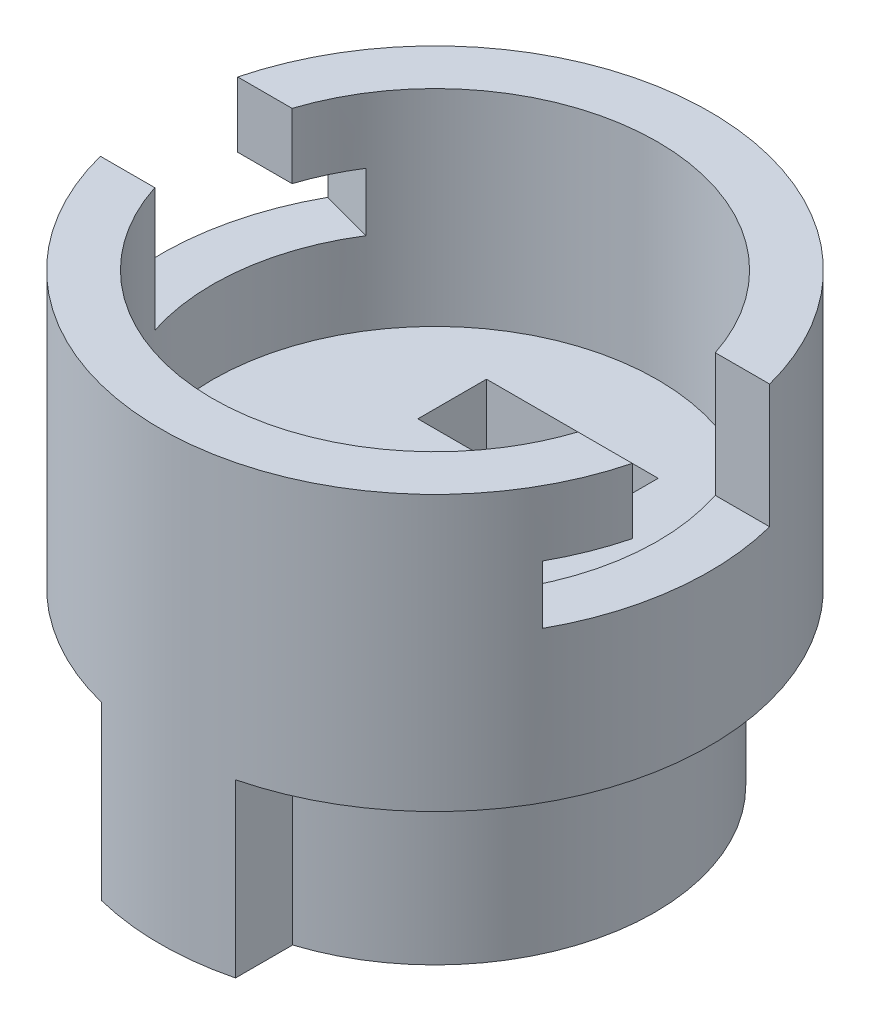
SolidWorks part; units mm, degrees
ref_plane "Front Plane" through (0, 0, 0) normal (0, 0, 1) x (1, 0, 0)
ref_plane "Top Plane" through (0, 0, 0) normal (0, 1, 0) x (1, 0, 0)
ref_plane "Right Plane" through (0, 0, 0) normal (1, 0, 0) x (0, 0, -1)
sketch "Sketch1" plane through (0, 0, 0) normal (0, 0, 1) x (1, 0, 0)
  line L0 (-8.128, 0) -> (-8.128, 6.35)
  line L2 (55, 0) -> (-55, 0) construction
  line L3 (-8.128, 6.35) -> (-10.16, 6.35)
  line L4 (-10.16, 6.35) -> (-10.16, 16.51)
  line L12 (-10.16, 16.51) -> (-8.128, 16.51)
  line L13 (0, 8.89) -> (0, 0) construction
  line L14 (-8.128, 16.51) -> (-8.128, 8.89)
  line L15 (-8.128, 8.89) -> (-6.096, 8.89)
  line L16 (-6.096, 6.35) -> (-6.096, 0)
  line L17 (-6.096, 0) -> (-8.128, 0)
  line L18 (-6.096, 8.89) -> (0, 8.89)
  line L19 (0, 8.89) -> (0, 6.35)
  line L20 (0, 6.35) -> (-6.096, 6.35)
  dimension "D1" = 6.35
  dimension "D2" = 8.128
  dimension "D3" = 2.032
  dimension "D4" = 10.16
  dimension "D6" = 2.54
  dimension "D5" = 2.032
  dimension "D7" = 2.54
  dimension "D8" = 2.032
revolve "Revolve1" add sketch "Sketch1" angle 360 about L13
sketch "Sketch4" plane through (0, 16.51, 0) normal (0, 1, 0) x (1, 0, 0)
  line L0 (-9.8374, 2.54) -> (-7.7209, 2.54)
  line L1 (-9.0805, 0) -> (9.0805, 0) construction
  line L2 (-9.8374, -2.54) -> (-7.7209, -2.54)
  line L3 (0, -9.0805) -> (0, 9.0805) construction
  line L4 (9.8374, -2.54) -> (7.7209, -2.54)
  line L5 (9.8374, 2.54) -> (7.7209, 2.54)
  circle A0 centre (0, 0) radius 10.16 construction
  circle A1 centre (0, 0) radius 8.128 construction
  circle A2 centre (0, 0) radius 8.128 construction
  arc A3 (-7.7209, 2.54) -> (-7.7209, -2.54) centre (0, 0) ccw
  arc A4 (-9.8374, 2.54) -> (-9.8374, -2.54) centre (0, 0) ccw
  arc A5 (7.7209, -2.54) -> (7.7209, 2.54) centre (0, 0) ccw
  arc A6 (9.8374, -2.54) -> (9.8374, 2.54) centre (0, 0) ccw
  dimension "D1" = 5.08
extrude "Cut-Extrude2" cut sketch "Sketch4" against normal blind 4.572
sketch "Sketch6" plane through (0, 16.51, 0) normal (0, 1, 0) x (1, 0, 0)
  line L0 (0, 0) -> (9.3592, 9.3592) construction
  line L1 (0, -9.0805) -> (0, 9.0805) construction
  line L2 (7.7209, -2.54) -> (9.8374, -2.54)
  line L3 (9.8374, 2.54) -> (7.7209, 2.54)
  line L4 (7.7209, -2.54) -> (9.8374, -2.54) construction
  line L5 (9.8374, 2.54) -> (7.7209, 2.54) construction
  line L6 (-7.7209, 2.54) -> (-9.8374, 2.54)
  line L7 (-9.8374, -2.54) -> (-7.7209, -2.54)
  line L8 (-7.7209, 2.54) -> (-9.8374, 2.54) construction
  line L9 (-9.8374, -2.54) -> (-7.7209, -2.54) construction
  line L14 (-2.475, 9.8539) -> (-2.475, 7.742)
  line L15 (2.475, 9.8539) -> (2.475, 7.742)
  line L16 (-9.0805, 0) -> (9.0805, 0) construction
  line L17 (2.475, -9.8539) -> (2.475, -7.742)
  line L18 (-2.475, -9.8539) -> (-2.475, -7.742)
  arc A2 (7.7209, -2.54) -> (7.7209, 2.54) centre (0, 0) ccw
  arc A3 (9.8374, -2.54) -> (9.8374, 2.54) centre (0, 0) ccw
  arc A4 (7.7209, -2.54) -> (7.7209, 2.54) centre (0, 0) ccw construction
  arc A5 (9.8374, -2.54) -> (9.8374, 2.54) centre (0, 0) ccw construction
  arc A6 (-7.7209, 2.54) -> (-7.7209, -2.54) centre (0, 0) ccw
  arc A7 (-9.8374, 2.54) -> (-9.8374, -2.54) centre (0, 0) ccw
  arc A8 (-7.7209, 2.54) -> (-7.7209, -2.54) centre (0, 0) ccw construction
  arc A9 (-9.8374, 2.54) -> (-9.8374, -2.54) centre (0, 0) ccw construction
  arc A12 (9.8374, 2.54) -> (-9.8374, 2.54) centre (0, 0) ccw construction
  arc A13 (7.7209, 2.54) -> (-7.7209, 2.54) centre (0, 0) ccw construction
  arc A14 (2.475, -9.8539) -> (-2.475, -9.8539) centre (0, 0) cw
  arc A15 (2.475, -7.742) -> (-2.475, -7.742) centre (0, 0) cw
  arc A16 (2.475, 9.8539) -> (-2.475, 9.8539) centre (0, 0) ccw
  arc A17 (2.475, 7.742) -> (-2.475, 7.742) centre (0, 0) ccw
  dimension "D3" = 45
  dimension "D4" = 4.95
  dimension "D1" = 0
  dimension "D2" = 0
extrude "Boss-Extrude1" add sketch "Sketch6" against normal up to surface (16.51 mm away) from offset 7.62 up to face at (-6.096, 0, 0) offset against normal yes
sketch "Sketch7" plane through (0, 16.51, 0) normal (0, 1, 0) x (1, 0, 0)
  circle A0 centre (0, 0) radius 8.228
  circle A1 centre (0, 0) radius 8.128 construction
  circle A2 centre (0, 0) radius 8.128
  dimension "D1" = 0.1
extrude "Cut-Extrude3" cut sketch "Sketch7" against normal up to surface (7.62 mm away)
sketch "Sketch8" plane through (0, 16.51, 0) normal (0, 1, 0) x (1, 0, 0)
  line L0 (7.8261, -2.54) -> (9.8374, -2.54) construction
  line L1 (9.8374, 2.54) -> (7.8261, 2.54) construction
  line L6 (-7.8261, 2.54) -> (-9.8374, 2.54) construction
  line L7 (-9.8374, -2.54) -> (-7.8261, -2.54) construction
  line L8 (7.8261, -2.54) -> (9.8374, -2.54) construction
  line L9 (9.8374, 2.54) -> (7.8261, 2.54) construction
  line L10 (-7.8261, 2.54) -> (-9.8374, 2.54)
  line L11 (-9.8374, -2.54) -> (-7.8261, -2.54) construction
  line L12 (-8.8884, 4.9216) -> (-6.9511, 4.4025)
  line L13 (-9.0805, 0) -> (9.0805, 0) construction
  line L14 (0, 2.54) -> (-11.3533, 5.5821) construction
  line L15 (-7.8261, 2.54) -> (0, 2.54) construction
  line L18 (8.8884, -4.9216) -> (6.9511, -4.4025)
  line L19 (7.8261, -2.54) -> (9.8374, -2.54)
  line L20 (0, -9.0805) -> (0, 9.0805) construction
  line L21 (-7.8261, -2.54) -> (7.8261, -2.54) construction
  line L22 (0, -2.54) -> (-11.3533, -5.5821) construction
  line L23 (0, -2.54) -> (11.3533, -5.5821) construction
  arc A0 (7.8261, -2.54) -> (7.8261, 2.54) centre (0, 0) ccw construction
  arc A1 (9.8374, -2.54) -> (9.8374, 2.54) centre (0, 0) ccw construction
  arc A6 (-7.8261, 2.54) -> (-7.8261, -2.54) centre (0, 0) ccw construction
  arc A7 (-9.8374, 2.54) -> (-9.8374, -2.54) centre (0, 0) ccw construction
  arc A8 (7.8261, -2.54) -> (7.8261, 2.54) centre (0, 0) ccw construction
  arc A9 (9.8374, -2.54) -> (9.8374, 2.54) centre (0, 0) ccw construction
  arc A10 (-7.8261, 2.54) -> (-7.8261, -2.54) centre (0, 0) ccw construction
  arc A11 (-9.8374, 2.54) -> (-9.8374, -2.54) centre (0, 0) ccw construction
  arc A12 (9.8374, 2.54) -> (-9.8374, 2.54) centre (0, 0) ccw construction
  arc A13 (7.8261, 2.54) -> (-7.8261, 2.54) centre (0, 0) ccw construction
  arc A14 (-6.9511, 4.4025) -> (-7.8261, 2.54) centre (0, 0) ccw
  arc A15 (-8.8884, 4.9216) -> (-9.8374, 2.54) centre (0, 0) ccw
  arc A18 (6.9511, -4.4025) -> (7.8261, -2.54) centre (0, 0) ccw
  arc A19 (8.8884, -4.9216) -> (9.8374, -2.54) centre (0, 0) ccw
  arc A20 (-9.8374, -2.54) -> (9.8374, -2.54) centre (0, 0) ccw construction
  arc A21 (-7.8261, -2.54) -> (7.8261, -2.54) centre (0, 0) ccw construction
  dimension "D1" = 15
extrude "Cut-Extrude4" cut sketch "Sketch8" against normal blind 2.159 from offset 2.413 offset against normal yes
sketch "Sketch9" plane through (0, 8.89, 0) normal (0, 1, 0) x (1, 0, 0)
  line L0 (0, -9.0805) -> (0, 9.0805) construction
  line L1 (-3.175, 5.08) -> (3.175, 5.08)
  line L2 (-3.175, 5.08) -> (-3.175, 2.54)
  line L3 (-3.175, 2.54) -> (3.175, 2.54)
  line L4 (3.175, 5.08) -> (3.175, 2.54)
  line L5 (-3.175, 5.08) -> (3.175, 2.54) construction
  line L6 (-3.175, 2.54) -> (3.175, 5.08) construction
  line L7 (-9.0805, 0) -> (9.0805, 0) construction
  line L8 (-3.175, -2.54) -> (3.175, -2.54)
  line L9 (3.175, -5.08) -> (3.175, -2.54)
  line L10 (-3.175, -5.08) -> (3.175, -5.08)
  line L11 (-3.175, -5.08) -> (-3.175, -2.54)
  point P0 (0, 3.81)
  dimension "D1" = 6.35
  dimension "D2" = 2.54
  dimension "D3" = 5.08
extrude "Cut-Extrude5" cut sketch "Sketch9" against normal up to next
